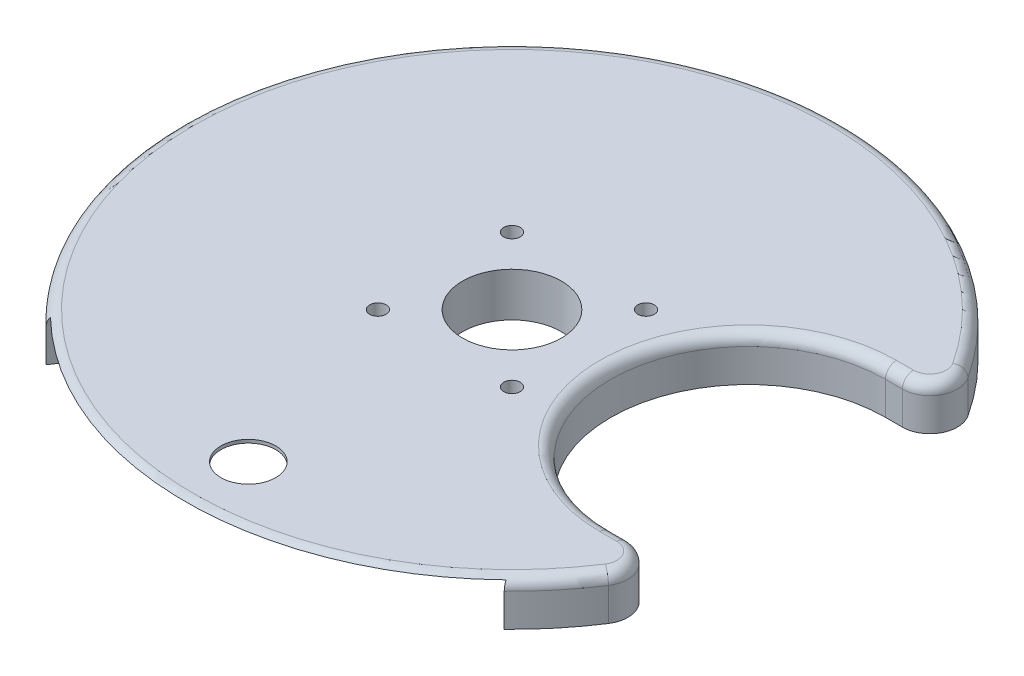
SolidWorks part; units mm, degrees
ref_plane "Front Plane" through (0, 0, 0) normal (0, 0, 1) x (1, 0, 0)
ref_plane "Top Plane" through (0, 0, 0) normal (0, 1, 0) x (1, 0, 0)
ref_plane "Right Plane" through (0, 0, 0) normal (1, 0, 0) x (0, 0, -1)
sketch "Sketch1" plane through (0, 0, 0) normal (0, 1, 0) x (1, 0, 0)
  line L0 (54.61, -31.75) -> (69.2703, -31.75)
  line L1 (-15.5, -15.5) -> (15.5, -15.5) construction
  line L2 (-15.5, -15.5) -> (-15.5, 15.5) construction
  line L3 (-15.5, 15.5) -> (15.5, 15.5) construction
  line L4 (15.5, -15.5) -> (15.5, 15.5) construction
  line L5 (-15.5, -15.5) -> (15.5, 15.5) construction
  line L6 (-15.5, 15.5) -> (15.5, -15.5) construction
  line L7 (54.61, 31.75) -> (69.2703, 31.75)
  line L8 (0, -54.61) -> (0, -60.96)
  line L9 (-70.2, 0) -> (-70.2, 6)
  line L10 (-70.2, 0) -> (-70.2, -6)
  line L11 (-70.2, 6) -> (-75.9634, 6)
  line L12 (-70.2, -6) -> (-75.9634, -6)
  line L13 (-27.3993, 64.9101) -> (-29.1803, 70.3914)
  line L14 (-21.693, 66.7642) -> (-15.9867, 68.6183)
  line L15 (-21.693, 66.7642) -> (-27.3993, 64.9101)
  line L16 (-15.9867, 68.6183) -> (-17.7676, 74.0996)
  line L17 (53.2663, 46.1166) -> (57.929, 49.5043)
  line L18 (56.793, 41.2625) -> (60.3197, 36.4084)
  line L19 (56.793, 41.2625) -> (53.2663, 46.1166)
  line L20 (60.3197, 36.4084) -> (64.9824, 39.7961)
  line L21 (60.3197, -36.4084) -> (64.9824, -39.7961)
  line L22 (56.793, -41.2625) -> (53.2663, -46.1166)
  line L23 (56.793, -41.2625) -> (60.3197, -36.4084)
  line L24 (53.2663, -46.1166) -> (57.929, -49.5043)
  line L25 (-15.9867, -68.6183) -> (-17.7676, -74.0996)
  line L26 (-21.693, -66.7642) -> (-27.3993, -64.9101)
  line L27 (-21.693, -66.7642) -> (-15.9867, -68.6183)
  line L28 (-27.3993, -64.9101) -> (-29.1803, -70.3914)
  circle A0 centre (0, 0) radius 76.2
  circle A1 centre (0, 0) radius 54.61 construction
  circle A2 centre (54.61, 0) radius 31.75
  circle A3 centre (0, -54.61) radius 25.4 construction
  circle A4 centre (0, -60.96) radius 6.35
  circle A7 centre (-15.5, 15.5) radius 1.905
  circle A8 centre (15.5, 15.5) radius 1.905
  circle A9 centre (15.5, -15.5) radius 1.905
  circle A10 centre (-15.5, -15.5) radius 1.905
  circle A11 centre (0, 0) radius 70.2
  circle A12 centre (0, 0) radius 11.43
  circle A13 centre (0, 0) radius 63.5
  circle A14 centre (0, -54.61) radius 19.05 construction
  point P28 (0, 0)
  point P56 (0, 0)
  point P60 (0, 0)
  dimension "D1" = 152.4
  dimension "D2" = 21.59
  dimension "D3" = 63.5
  dimension "D6" = 50.8
  dimension "D7" = 6.35
  dimension "D8" = 12.7
  dimension "D9" = 3.81
  dimension "D11" = 6
  dimension "D15" = 22.86
  dimension "D16" = 12.7
  dimension "D17" = 38.1
  dimension "D4" = 31
  dimension "D5" = 31
  dimension "D12" = 6
  dimension "D13" = 6
  dimension "D10" = 4
  dimension "D14" = 5
extrude "Boss-Extrude1" add sketch "Sketch1" along normal blind 10.16 contours A4 A13 L0 A2 L7 A12 A10 A9 A8 A7 | A13 L7 A11 L0 | A11 L15 L13 A0 L11 L9 | A11 L19 L17 A0 L16 L14 | A11 L7 A0 L20 L18 | A11 L10 L12 A0 L28 L26 | A11 L27 L25 A0 L24 L22 | A11 L23 L21 A0 L0 | A10 | A9 | L11 A0 L12 L10 L9 | L16 A0 L13 L15 L14 | L20 A0 L17 L19 L18 | L24 A0 L21 L23 L22 | L28 A0 L25 L27 L26
sketch "Sketch8" plane through (0, 0, 0) normal (0, -1, 0) x (1, 0, 0)
  line L0 (25.3622, 24.9859) -> (62.6107, 43.4321)
  arc A0 (-52.9795, 54.7687) -> (52.9795, 54.7688) centre (0, 76.2) ccw
  arc A1 (69.2703, 31.75) -> (69.2703, -31.75) centre (0, 0) ccw construction
  circle A2 centre (0, 0) radius 76.2
  arc A3 (69.2703, 31.75) -> (69.2703, -31.75) centre (0, 0) ccw construction
  arc A4 (69.2703, 31.75) -> (69.2703, -31.75) centre (0, 0) ccw
  arc A5 (69.2703, 31.75) -> (69.2703, -31.75) centre (0, 0) ccw construction
  spline S0 degree 2 poles (27.1675, 25.9203) (-19.3552, 3.3848) (-52.9795, 54.7687) knots 0 0 0 1 1 1
  circle M2 centre (0, 60.96) radius 6.35
  arc M14 (69.2703, 31.75) -> (69.2703, -31.75) centre (0, 0) ccw
  dimension "D1" = 57.15
extrude "Cut-Extrude3" cut sketch "Sketch8" against normal blind 9.398 contours S0 A0 M14 M2 | A2
fillet "Fillet1" radius 6.35 2 edges at (69.2703, 5.08, 31.75) (69.2703, 5.08, -31.75)
fillet "Fillet3" radius 2.54 6 edges at (56.5771, 10.16, -31.75) (64.1261, 10.16, -35.0728) (-76.2, 10.16, 0) (64.1261, 10.16, 35.0728) (56.5771, 10.16, 31.75) (22.86, 10.16, 0)
